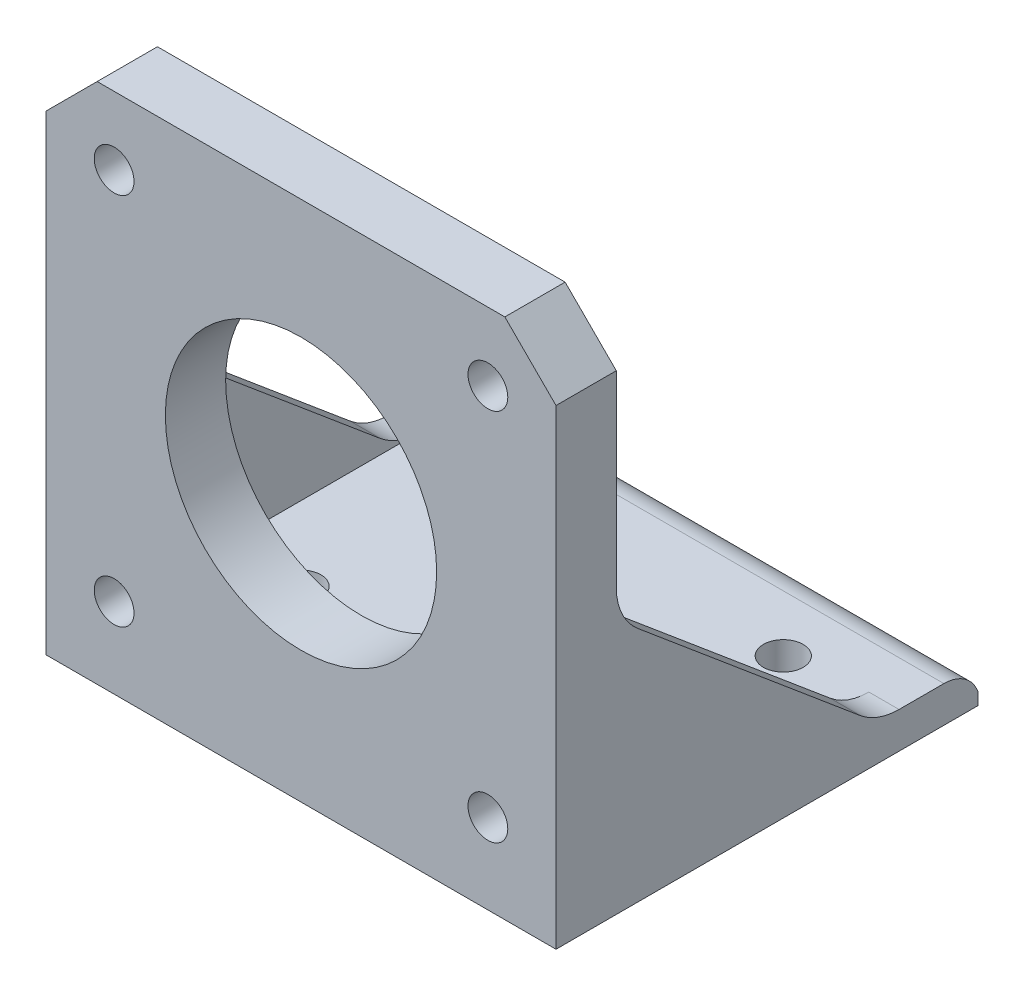
SolidWorks part; units mm, degrees
ref_plane "Front Plane" through (0, 0, 0) normal (0, 0, 1) x (1, 0, 0)
ref_plane "Top Plane" through (0, 0, 0) normal (0, 1, 0) x (1, 0, 0)
ref_plane "Right Plane" through (0, 0, 0) normal (1, 0, 0) x (0, 0, -1)
sketch "Sketch2" plane through (0, 0, 0) normal (0, 0, 1) x (1, 0, 0)
  line L0 (-21.15, 16.9074) -> (-16.9074, 21.15)
  line L1 (-16.9074, 21.15) -> (16.9074, 21.15)
  line L2 (16.9074, 21.15) -> (21.15, 16.9074)
  line L3 (21.15, 16.9074) -> (21.15, -16.9074)
  line L4 (21.15, -16.9074) -> (16.9074, -21.15) construction
  line L5 (16.9074, -21.15) -> (-16.9074, -21.15)
  line L6 (-16.9074, -21.15) -> (-21.15, -16.9074) construction
  line L7 (-21.15, -16.9074) -> (-21.15, 16.9074)
  line L8 (-15.5, 21.15) -> (-15.5, 15.5) construction
  line L9 (-15.5, 15.5) -> (-21.15, 15.5) construction
  line L10 (-21.15, 0) -> (21.15, 0) construction
  line L11 (0, 21.15) -> (0, -21.15) construction
  line L12 (-21.15, -16.9074) -> (-21.15, -21.15)
  line L13 (-21.15, -21.15) -> (-16.9074, -21.15)
  line L14 (16.9074, -21.15) -> (21.15, -21.15)
  line L15 (21.15, -21.15) -> (21.15, -16.9074)
  circle A0 centre (-15.5, 15.5) radius 1.65
  circle A1 centre (0, 0) radius 11.25
  circle A2 centre (15.5, 15.5) radius 1.65
  circle A3 centre (15.5, -15.5) radius 1.65
  circle A4 centre (-15.5, -15.5) radius 1.65
  point P28 (0, 0)
  dimension "D4" = 3.3
  dimension "D6" = 22.5
  dimension "D1" = 45
  dimension "D2" = 6
  dimension "D3" = 42.3
  dimension "D5" = 5.65
  dimension "D7" = 4
extrude "Boss-Extrude2" add sketch "Sketch2" along normal mid plane 5
sketch "Sketch7" plane through (0, -21.15, 0) normal (0, -1, 0) x (1, 0, 0)
  line L0 (-21.15, 2.5) -> (-21.15, -2.5) construction
  line L1 (21.15, 2.5) -> (-21.15, 2.5)
  line L2 (21.15, 2.5) -> (21.15, -32.5)
  line L3 (21.15, -32.5) -> (-21.15, -32.5)
  line L4 (-21.15, 2.5) -> (-21.15, -32.5)
  line L5 (-21.15, -2.5) -> (21.15, -2.5) construction
  dimension "D1" = 30
extrude "Boss-Extrude5" add sketch "Sketch7" against normal blind 2
sketch "Sketch10" plane through (21.15, 0, 0) normal (1, 0, 0) x (0, 0, -1)
  line L0 (24.1303, -19.15) -> (2.5, -1)
  line L1 (2.5, -19.15) -> (2.5, 16.9074) construction
  line L2 (2.5, -1) -> (2.5, -19.15)
  line L3 (2.5, -19.15) -> (24.1303, -19.15)
  line L5 (32.5, -19.15) -> (2.5, -19.15) construction
  dimension "D2" = 50
extrude "Boss-Extrude6" add sketch "Sketch10" against normal blind 2.5
mirror "Mirror2" about plane through (0, 0, 0) normal (1, 0, 0) of "Boss-Extrude6"
fillet "Fillet2" radius 5 4 edges at (19.9, -19.15, -24.1303) (-19.9, -19.15, -24.1303) (-19.9, -1, -2.5) (19.9, -1, -2.5)
fillet "Fillet3" radius 3 1 edges at (0, -19.15, -32.5)
sketch "Sketch11" plane through (0, -19.15, 0) normal (0, 1, 0) x (1, 0, 0)
  line L0 (12.5, 32.5) -> (12.5, 25) construction
  line L1 (-21.15, 32.5) -> (21.15, 32.5) construction
  line L2 (12.5, 25) -> (12.5, 17.5) construction
  line L3 (12.5, 17.5) -> (12.5, 10) construction
  line L4 (12.5, 10) -> (12.5, 2.5) construction
  line L5 (16.9074, 2.5) -> (-16.9074, 2.5) construction
  line L6 (0, 0) -> (0, 12.9734) construction
  circle A0 centre (12.5, 10) radius 1.65
  circle A1 centre (12.5, 25) radius 1.65
  circle A2 centre (-12.5, 25) radius 1.65
  circle A3 centre (-12.5, 10) radius 1.65
  dimension "D1" = 3.3
  dimension "D2" = 12.5
extrude "Cut-Extrude1" cut sketch "Sketch11" against normal up to surface (2 mm away) up to face at (0, -21.15, -15)
sketch "Sketch12" plane through (0, -21.15, 0) normal (0, -1, 0) x (1, 0, 0)
  line L4 (-21.15, 2.5) -> (-21.15, -32.5)
  line L5 (-21.15, -32.5) -> (21.15, -32.5)
  line L6 (21.15, -32.5) -> (21.15, 2.5)
  line L7 (21.15, 2.5) -> (-21.15, 2.5)
  line L8 (-21.15, 2.5) -> (-21.15, -32.5)
  line L9 (-21.15, -32.5) -> (21.15, -32.5)
  line L10 (21.15, -32.5) -> (21.15, 2.5)
  line L11 (21.15, 2.5) -> (-21.15, 2.5)
  circle A0 centre (-12.5, -25) radius 1.65 construction
  circle A1 centre (-12.5, -10) radius 1.65 construction
  circle A2 centre (12.5, -10) radius 1.65 construction
  circle A3 centre (12.5, -25) radius 1.65 construction
  circle A4 centre (-12.5, -25) radius 1.65
  circle A5 centre (-12.5, -10) radius 1.65
  circle A6 centre (12.5, -10) radius 1.65
  circle A7 centre (12.5, -25) radius 1.65
  dimension "D1" = 0
extrude "Boss-Extrude7" add sketch "Sketch12" along normal blind 1
